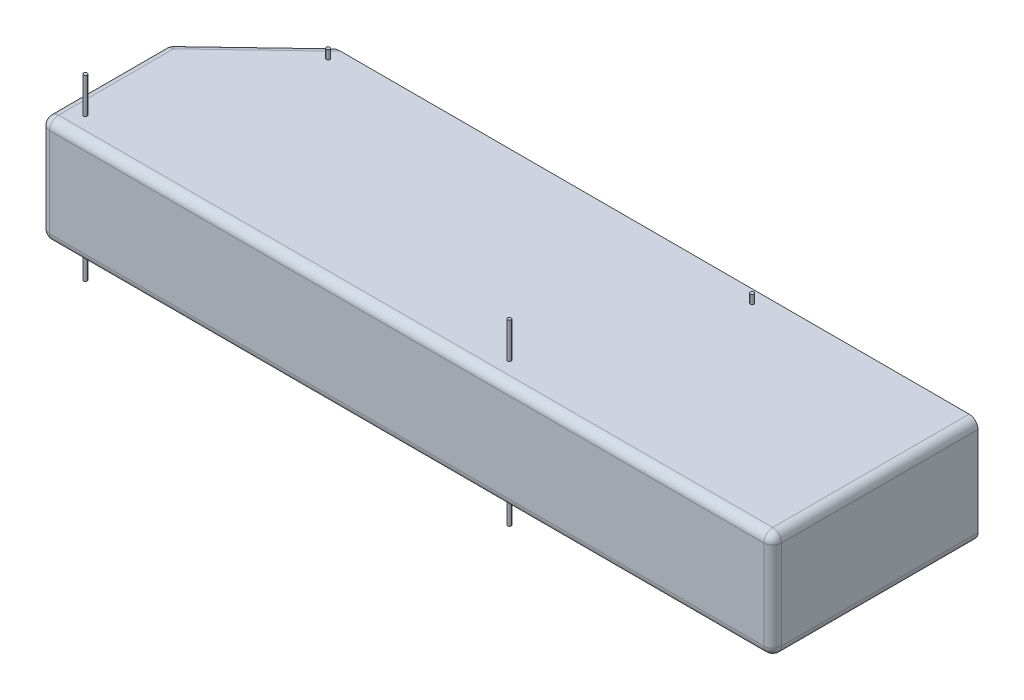
SolidWorks part; units mm, degrees
ref_plane "Front Plane" through (0, 0, 0) normal (0, 0, 1) x (1, 0, 0)
ref_plane "Top Plane" through (0, 0, 0) normal (0, 1, 0) x (1, 0, 0)
ref_plane "Right Plane" through (0, 0, 0) normal (1, 0, 0) x (0, 0, -1)
sketch "Sketch1" plane through (0, 0, 0) normal (0, 0, 1) x (1, 0, 0)
  line L3 (400, 60) -> (-400, 60)
  line L4 (410, 50) -> (410, -50)
  line L5 (400, -60) -> (-400, -60)
  line L6 (-410, 50) -> (-410, -50)
  line L7 (410, 60) -> (-410, -60) construction
  line L8 (410, -60) -> (-410, 60) construction
  arc A2 (-400, -60) -> (-410, -50) centre (-400, -50) cw
  arc A3 (-400, 60) -> (-410, 50) centre (-400, 50) ccw
  arc A4 (410, 50) -> (400, 60) centre (400, 50) ccw
  arc A5 (400, -60) -> (410, -50) centre (400, -50) ccw
  point P0 (0, 0)
  dimension "D1" = 10
  dimension "D2" = 10
  dimension "D3" = 10
  dimension "D4" = 10
  dimension "D5" = 800
  dimension "D6" = 100
extrude "Boss-Extrude1" add sketch "Sketch1" along normal blind 230
fillet "Fillet1" radius 10 8 edges at (-407.0711, -57.0711, 230) (-410, 0, 230) (-407.0711, 57.0711, 230) (0, 60, 230) (407.0711, 57.0711, 230) (410, 0, 230) (407.0711, -57.0711, 230) (0, -60, 230)
sketch "Sketch2" plane through (0, -60, 0) normal (0, -1, 0) x (1, 0, 0)
  line L0 (400, 220) -> (-400, 220) construction
  line L1 (-400, 220) -> (-400, 0) construction
  line L2 (400, 220) -> (400, 0) construction
  line L3 (90, 205) -> (90, 14) construction
  line L4 (90, 14) -> (171, 14) construction
  line L5 (-385, 205) -> (-385, 14) construction
  line L6 (-385, 14) -> (-304, 14) construction
  circle A0 centre (-385, 205) radius 2
  circle A1 centre (90, 205) radius 2
  circle A2 centre (171, 14) radius 2
  circle A3 centre (-304, 14) radius 2
  dimension "D1" = 4
  dimension "D4" = 4
  dimension "D8" = 4
  dimension "D9" = 4
  dimension "D2" = 15
  dimension "D3" = 15
  dimension "D5" = 15
  dimension "D6" = 310
  dimension "D7" = 81
extrude "Boss-Extrude2" add sketch "Sketch2" along normal blind 40
sketch "Sketch3" plane through (0, 60, 0) normal (0, 1, 0) x (1, 0, 0)
  line L0 (-400, -220) -> (400, -220) construction
  line L1 (90, -205) -> (90, -14) construction
  line L2 (-400, -220) -> (-400, 0) construction
  line L3 (400, -220) -> (400, 0) construction
  line L4 (90, -14) -> (171, -14) construction
  line L5 (-385, -205) -> (-385, -14) construction
  line L6 (-385, -14) -> (-304, -14) construction
  circle A0 centre (-385, -205) radius 2
  circle A1 centre (90, -205) radius 2
  circle A2 centre (171, -14) radius 2
  circle A3 centre (-304, -14) radius 2
  dimension "D1" = 4
  dimension "D4" = 4
  dimension "D7" = 4
  dimension "D8" = 4
  dimension "D2" = 15
  dimension "D3" = 15
  dimension "D5" = 15
  dimension "D6" = 310
extrude "Boss-Extrude3" add sketch "Sketch3" along normal blind 40
sketch "Sketch5" plane through (0, -60, 0) normal (0, -1, 0) x (1, 0, 0)
  line L5 (-318.5527, 0) -> (-432.2204, 108.2369)
  line L6 (-400, 0) -> (400, 0) construction
  line L7 (-432.2204, 108.2369) -> (-432.2204, 0)
  line L8 (-432.2204, 0) -> (-318.5527, 0)
extrude "Cut-Extrude2" cut sketch "Sketch5" against normal blind 150
fillet "Fillet2" radius 10 5 edges at (-359.2764, 60, 38.7779) (-407.0711, 57.0711, 84.2891) (-410, 0, 87.0781) (-407.0711, -57.0711, 84.2891) (-359.2764, -60, 38.7779)
sketch "Sketch8" plane through (0, -100, 0) normal (0, -1, 0) x (1, 0, 0)
  circle A0 centre (-304, 14) radius 2
extrude "Cut-Extrude3" cut sketch "Sketch8" against normal blind 30
sketch "Sketch9" plane through (0, -100, 0) normal (0, -1, 0) x (1, 0, 0)
  circle A0 centre (171, 14) radius 2
extrude "Cut-Extrude4" cut sketch "Sketch9" against normal blind 30
sketch "Sketch10" plane through (0, 100, 0) normal (0, 1, 0) x (1, 0, 0)
  circle A0 centre (171, -14) radius 2.6462
extrude "Cut-Extrude5" cut sketch "Sketch10" against normal blind 30
sketch "Sketch11" plane through (0, 100, 0) normal (0, 1, 0) x (1, 0, 0)
  circle A0 centre (-304, -14) radius 7.4287
extrude "Cut-Extrude6" cut sketch "Sketch11" against normal blind 30
